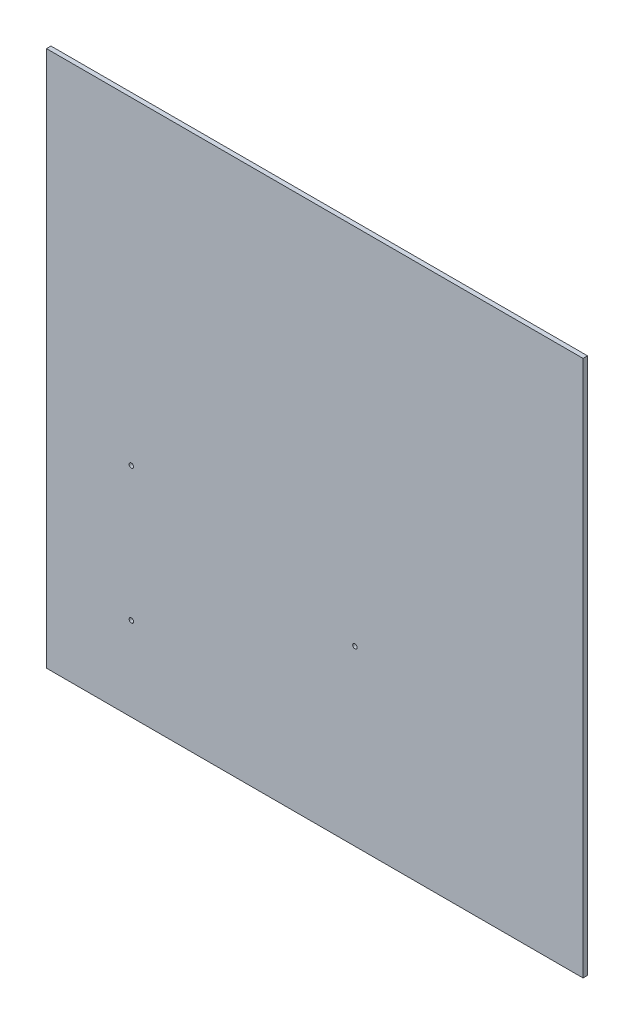
SolidWorks part; units mm, degrees
material "Maple"
ref_plane "Front Plane" through (0, 0, 0) normal (0, 0, 1) x (1, 0, 0)
ref_plane "Top Plane" through (0, 0, 0) normal (0, 1, 0) x (1, 0, 0)
ref_plane "Right Plane" through (0, 0, 0) normal (1, 0, 0) x (0, 0, -1)
sketch "Sketch1" plane through (0, 0, 0) normal (0, 0, 1) x (1, 0, 0)
  line L1 (0, 0) -> (304.8, 0)
  line L2 (0, 0) -> (0, 304.8)
  line L3 (0, 304.8) -> (304.8, 304.8)
  line L4 (304.8, 0) -> (304.8, 304.8)
  dimension "D1" = 304.8
  dimension "D2" = 304.8
extrude "Boss-Extrude1" add sketch "Sketch1" along normal blind 2.54
sketch "Sketch2" plane through (0, 0, 2.54) normal (0, 0, 1) x (1, 0, 0)
  circle A2 centre (48.205, 47.5897) radius 1.27
  circle A3 centre (175.205, 98.3897) radius 1.27
  circle A4 centre (48.205, 123.7897) radius 1.27
  dimension "D1" = 2.54
  dimension "D2" = 2.54
  dimension "D3" = 127
  dimension "D4" = 50.8
  dimension "D5" = 76.2
extrude "Cut-Extrude1" cut sketch "Sketch2" against normal through all both and the other way through all
